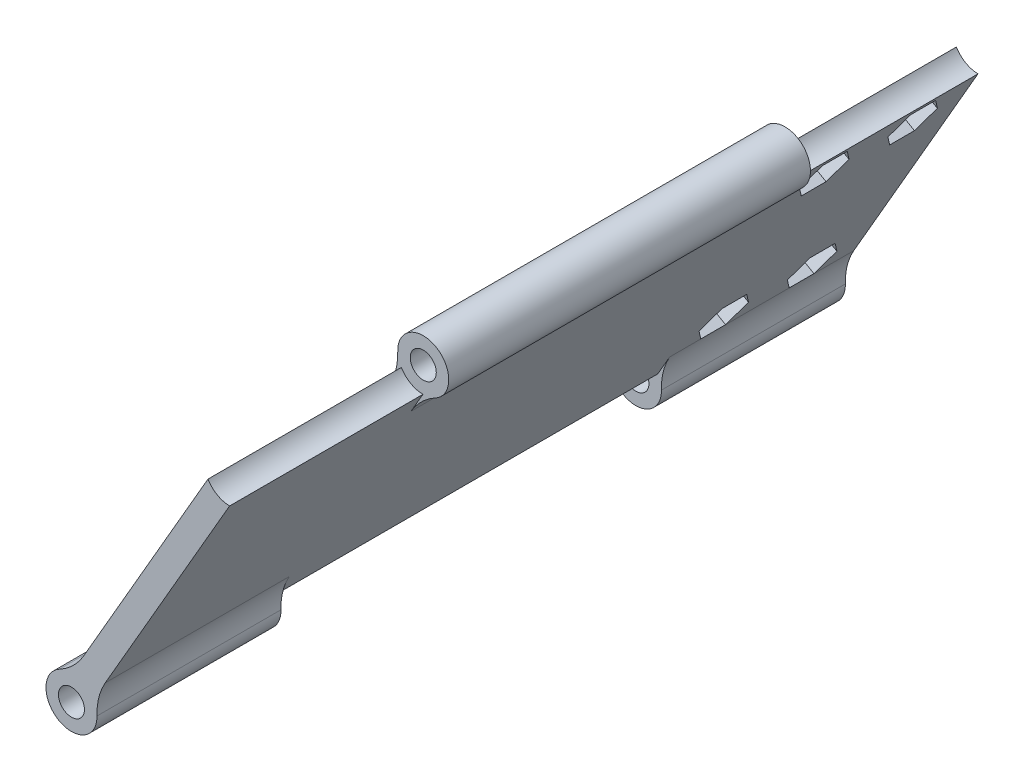
SolidWorks part; units mm, degrees
material "PLA"
ref_plane "Front Plane" through (0, 0, 0) normal (0, 0, 1) x (1, 0, 0)
ref_plane "Top Plane" through (0, 0, 0) normal (0, 1, 0) x (1, 0, 0)
ref_plane "Right Plane" through (0, 0, 0) normal (1, 0, 0) x (0, 0, -1)
sketch "Sketch2" plane through (0, 0, 0) normal (0, 0, 1) x (1, 0, 0)
  line L0 (0, 0) -> (38.1, 0)
  line L1 (0, 0) -> (0, -38.1)
  circle A0 centre (0, 0) radius 38.1
  circle A1 centre (0, -29.337) radius 1.5875
  circle A2 centre (-25.4066, 14.6685) radius 1.5875
  circle A3 centre (25.4066, 14.6685) radius 1.5875
  point P13 (0, 0)
  dimension "D1" = 76.2
  dimension "D2" = 3.175
  dimension "D3" = 8.763
  dimension "D4" = 3
extrude "Boss-Extrude1" add sketch "Sketch2" along normal blind 10 contours A1 L1 L0 A0 A3 A2 | A1 L1 A0 L0 region at (-5.4206, 5.3873, 0) region at (16.2241, -16.1243, 0)
sketch "Sketch3" plane through (0, 0, 10) normal (0, 0, 1) x (1, 0, 0)
  line L1 (0, -29.337) -> (25.4066, 14.6685)
  line L2 (1.7321, -30.337) -> (27.1386, 13.6685)
  line L3 (-1.7321, -28.337) -> (23.6745, 15.6685)
  circle A11 centre (0, -29.337) radius 1.5875
  circle A12 centre (25.4066, 14.6685) radius 1.5875
  circle A17 centre (0, -29.337) radius 2.0875
  circle A18 centre (25.4066, 14.6685) radius 2.0875
  circle A19 centre (0, -29.337) radius 4.0875
  circle A20 centre (25.4066, 14.6685) radius 4.0875
  dimension "D1" = 0.5
  dimension "D2" = 2
  dimension "D4" = 2
  dimension "D5" = 2
extrude "Boss-Extrude2" add sketch "Sketch3" along normal blind 120 separate body contours L2 A20 L3 A18 | L1 A20 L2 A18 | L3 A20 L1 A18 | A20 L1 A19 L2 | A20 L3 A19 L1 | L1 A19 L3 A17 | L2 A19 L1 A17 | L3 A19 L2 A17 region at (0.4725, -26.4041, 10) region at (2.3037, -27.4614, 10) region at (11.8338, -6.8323, 10) region at (13.5728, -7.8362, 10) region at (-1.1016, -31.245, 10) region at (23.1028, 12.7929, 10) region at (24.9341, 11.7356, 10) region at (24.355, 18.4986, 10)
delete or keep bodies "Body-Delete/Keep 2" type delete bodies bodies 101
ref_plane "Plane1" through (0, 0, 70) normal (0, 0, 1) x (1, 0, 0)
sketch "Sketch4" plane through (0, 0, 70) normal (0, 0, 1) x (1, 0, 0)
  circle A1 centre (0, -29.337) radius 4.0875
extrude "Cut-Extrude1" cut sketch "Sketch4" against normal blind 30.5 and the other way blind 30.5 contours A1
sketch "Sketch5" plane through (0, 0, 10) normal (0, 0, -1) x (-1, 0, 0)
  circle A0 centre (-25.4066, 14.6685) radius 4.0875
extrude "Cut-Extrude2" cut sketch "Sketch5" against normal offset from surface (31 mm away) 1.5 up to face at (2.0875, -29.337, 39.5) offset beyond the face yes
sketch "Sketch6" plane through (0, 0, 130) normal (0, 0, 1) x (1, 0, 0)
  circle A0 centre (25.4066, 14.6685) radius 4.0875
extrude "Cut-Extrude3" cut sketch "Sketch6" against normal offset from surface (31 mm away) 1.5 contours A0 up to face at (2.0875, -29.337, 100.5) offset beyond the face yes
fillet "Fillet1" radius 10 6 edges at (21.8921, 12.5813, 70) (0.0503, -25.2498, 24.75) (0.0503, -25.2498, 115.25) (3.5144, -27.2498, 115.25) (3.5144, -27.2498, 24.75) (25.3562, 10.5813, 70)
sketch "Sketch7" plane through (10.9712, -6.3343, 0) normal (-0.866, 0.5, 0) x (0, 0, 1)
  circle A0 centre (18.3842, -14.5821) radius 1.5
  circle A1 centre (32.5542, -14.5821) radius 1.5
  circle A2 centre (18.3842, 17.6479) radius 1.5
  circle A3 centre (32.5542, 17.6479) radius 1.5
extrude "Cut-Extrude4" cut sketch "Sketch7" against normal up to surface (4 mm away) contours A0 | A2 | A3 | A1 | A0 region at (3.6802, -18.9627, 18.3842) region at (19.7952, 8.9493, 18.3842) region at (19.7952, 8.9493, 32.5542) up to face at (14.7532, -7.7836, 70)
sketch "Sketch8" plane through (14.4353, -8.3342, 0) normal (0.866, -0.5, 0) x (0, 0, -1)
  line L25 (-28.5948, 17.6686) -> (-30.5924, 21.0872)
  line L26 (-30.5924, 21.0872) -> (-34.5518, 21.0665)
  line L27 (-34.5518, 21.0665) -> (-36.5137, 17.6272)
  line L28 (-36.5137, 17.6272) -> (-34.5161, 14.2086)
  line L29 (-34.5161, 14.2086) -> (-30.5566, 14.2293)
  line L30 (-30.5566, 14.2293) -> (-28.5948, 17.6686)
  line L31 (-14.4248, 17.6686) -> (-16.4224, 21.0872)
  line L32 (-16.4224, 21.0872) -> (-20.3818, 21.0665)
  line L33 (-20.3818, 21.0665) -> (-22.3437, 17.6272)
  line L34 (-22.3437, 17.6272) -> (-20.3461, 14.2086)
  line L35 (-20.3461, 14.2086) -> (-16.3866, 14.2293)
  line L36 (-16.3866, 14.2293) -> (-14.4248, 17.6686)
  line L37 (-14.4248, -14.5614) -> (-16.4224, -11.1428)
  line L38 (-16.4224, -11.1428) -> (-20.3818, -11.1635)
  line L39 (-20.3818, -11.1635) -> (-22.3437, -14.6028)
  line L40 (-22.3437, -14.6028) -> (-20.3461, -18.0214)
  line L41 (-20.3461, -18.0214) -> (-16.3866, -18.0007)
  line L42 (-16.3866, -18.0007) -> (-14.4248, -14.5614)
  line L43 (-28.5948, -14.5614) -> (-30.5924, -11.1428)
  line L44 (-30.5924, -11.1428) -> (-34.5518, -11.1635)
  line L45 (-34.5518, -11.1635) -> (-36.5137, -14.6028)
  line L46 (-36.5137, -14.6028) -> (-34.5161, -18.0214)
  line L47 (-34.5161, -18.0214) -> (-30.5566, -18.0007)
  line L48 (-30.5566, -18.0007) -> (-28.5948, -14.5614)
  circle A0 centre (-32.5542, 17.6479) radius 3.429 construction
  circle A1 centre (-18.3842, 17.6479) radius 3.429 construction
  circle A2 centre (-18.3842, -14.5821) radius 3.429 construction
  circle A3 centre (-32.5542, -14.5821) radius 3.429 construction
  circle M4 centre (-32.5542, 17.6479) radius 1.5
  circle M5 centre (-18.3842, 17.6479) radius 1.5
  circle M6 centre (-18.3842, -14.5821) radius 1.5
  dimension "D1" = 6.858
extrude "Cut-Extrude5" cut sketch "Sketch8" against normal blind 2 contours L29 L30 L25 L26 L27 L28 M6 | L47 L48 L43 L44 L45 L46 M5 | L41 L42 L37 L38 L39 L40 M4 | L35 L36 L31 L32 L33 L34 region at (22.4358, 5.5229, 29.6668) region at (6.3208, -22.3891, 15.4968) region at (7.1443, -20.9627, 32.5542)
